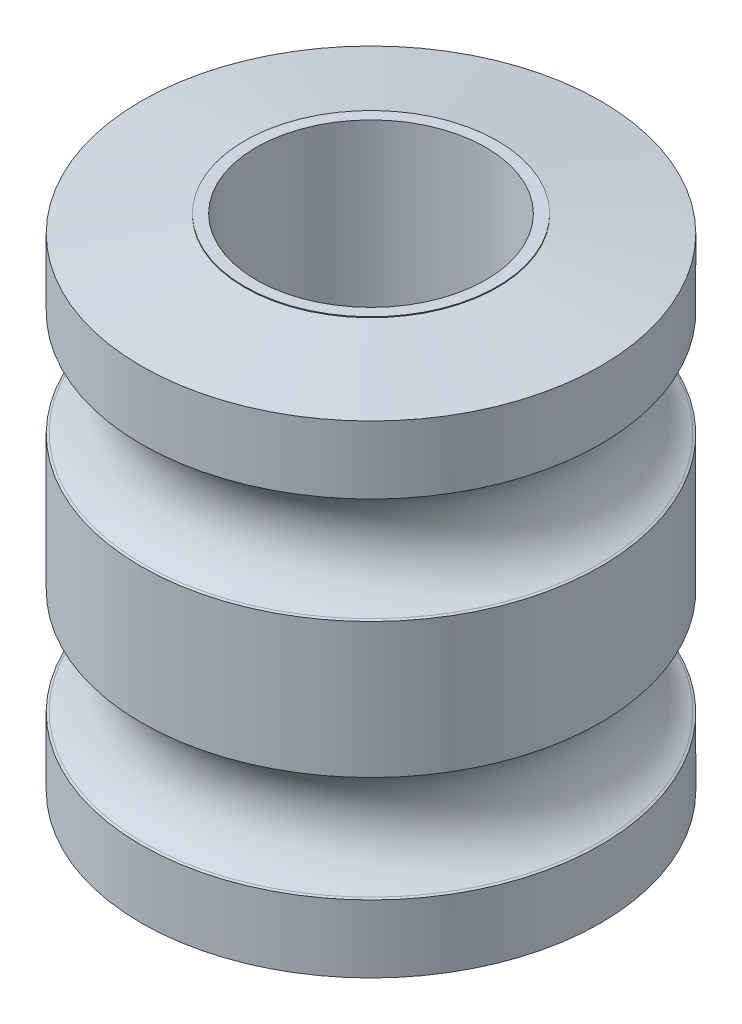
SolidWorks part; units mm, degrees
ref_plane "Front Plane" through (0, 0, 0) normal (0, 0, 1) x (1, 0, 0)
ref_plane "Top Plane" through (0, 0, 0) normal (0, 1, 0) x (1, 0, 0)
ref_plane "Right Plane" through (0, 0, 0) normal (1, 0, 0) x (0, 0, -1)
sketch "Sketch1" plane through (0, 0, 0) normal (0, 1, 0) x (1, 0, 0)
  circle A0 centre (0, 0) radius 5.08
  circle A1 centre (0, 0) radius 2.54
  dimension "D1" = 10.16
  dimension "D2" = 5.08
extrude "Boss-Extrude1" add sketch "Sketch1" along normal blind 2.667
chamfer "Chamfer3" distance 2.5146 angle 25 1 edges at (0, 0, 5.08) first distance on face at (0, 0, 5.08)
mirror "Mirror4" about plane through (0, 0, 0) normal (0, 1, 0) of bodies 101 102
sketch "Sketch3" plane through (0, 2.667, 0) normal (0, 1, 0) x (1, 0, 0)
  circle A0 centre (0, 0) radius 2.794
  circle A1 centre (0, 0) radius 2.54
  dimension "D1" = 5.588
extrude "Boss-Extrude2" add sketch "Sketch3" along normal blind 0.381
chamfer "Chamfer1" distance 2.286 angle 9 1 edges at (0, 2.667, 2.794) first distance on face at (0, 2.667, 5.08)
sketch3d "3DSketch1"
  point P0 (-1.3698, 3.039, -4.8918)
ref_plane "Plane1" through (-0.8484, 0.1457, -5.0625) normal (-0.1652, 0.0284, -0.9858) x (-0.9838, 0.0657, 0.1668)
sketch "Sketch4" plane through (-0.8484, 0.1457, -5.0625) normal (-0.1652, 0.0284, -0.9858) x (-0.9838, 0.0657, 0.1668)
  line L0 (0, 3.7604) -> (0.6151, 3.714)
  line L9 (0.6151, 3.714) -> (0.6151, 2.6791)
  line L10 (0.6151, 2.6791) -> (0, 2.6791)
  line L11 (0, 2.6791) -> (0, 3.7604)
  line L12 (-0.5687, -3.008) -> (0.2572, -3.0624)
  line L13 (0.2572, -3.0624) -> (0.2158, -3.6916)
  line L14 (0.2158, -3.6916) -> (-0.6129, -3.633)
  line L15 (-0.5687, -3.008) -> (-0.6129, -3.633)
  point P5 (0, 0)
  point P6 (0, 3.6601)
  point P7 (-1.2261, -3.5896)
  point P10 (0.6151, 3.7604)
  point P11 (-0.0604, 3.7604)
  point P12 (0.6151, 2.6791)
  point P13 (0, 2.6791)
  point P14 (0, 3.7604)
  point P16 (0.6151, 3.714)
mirror "Mirror5" about plane through (0, -2.667, 0) normal (0, -1, 0) of bodies 102
fillet "Fillet4" radius 1.27 2 edges at (0, -5.334, 2.5654) (0, 0, 2.5654)
